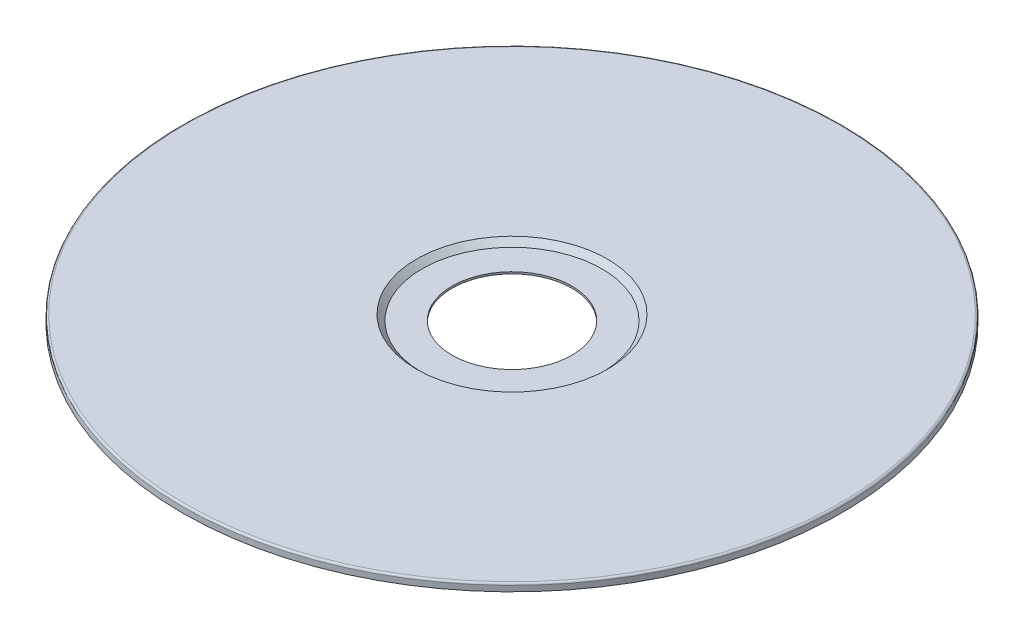
SolidWorks part; units mm, degrees
ref_plane "Front Plane" through (0, 0, 0) normal (0, 0, 1) x (1, 0, 0)
ref_plane "Top Plane" through (0, 0, 0) normal (0, 1, 0) x (1, 0, 0)
ref_plane "Right Plane" through (0, 0, 0) normal (1, 0, 0) x (0, 0, -1)
sketch "Sketch1" plane through (0, 0, 0) normal (0, 1, 0) x (1, 0, 0)
  circle A0 centre (0, 0) radius 203.2
  circle A1 centre (0, 0) radius 1117.6
extrude "Boss-Extrude1" add sketch "Sketch1" along normal blind 25.4
sketch "Sketch2" plane through (0, 25.4, 0) normal (0, 1, 0) x (1, 0, 0)
  circle A0 centre (0, 0) radius 304.8
extrude "Cut-Extrude1" cut sketch "Sketch2" against normal blind 19.05
chamfer "Chamfer1" distance 19.05 angle 45 1 edges at (0, 25.4, 304.8)
fillet "Fillet1" radius 6.35 1 edges at (0, 25.4, 1117.6)
